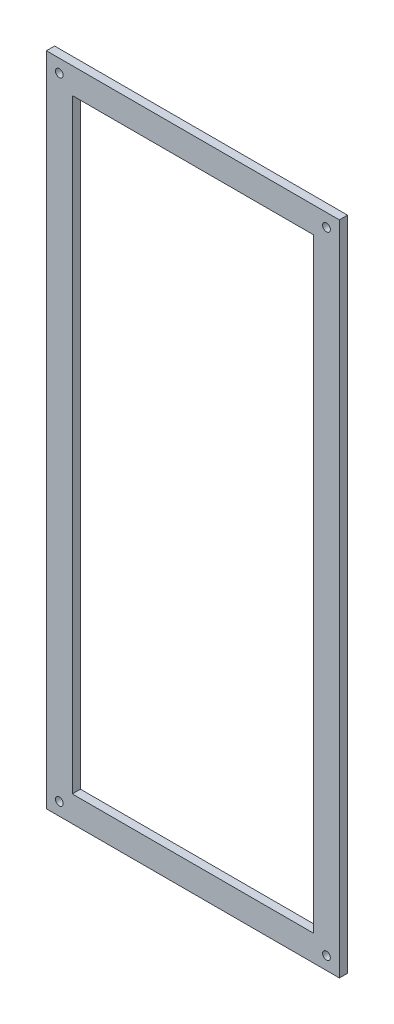
SolidWorks part; units mm, degrees
ref_plane "Front Plane" through (0, 0, 0) normal (0, 0, 1) x (1, 0, 0)
ref_plane "Top Plane" through (0, 0, 0) normal (0, 1, 0) x (1, 0, 0)
ref_plane "Right Plane" through (0, 0, 0) normal (1, 0, 0) x (0, 0, -1)
sketch "Sketch1" plane through (0, 0, 0) normal (0, 0, 1) x (1, 0, 0)
  line L0 (0, 0) -> (0, 254)
  line L1 (0, 254) -> (113.35, 254)
  line L2 (113.35, 254) -> (113.35, 0)
  line L3 (113.35, 0) -> (0, 0)
  line L4 (10, 10) -> (10, 244)
  line L5 (10, 244) -> (103.35, 244)
  line L6 (103.35, 244) -> (103.35, 10)
  line L7 (103.35, 10) -> (10, 10)
  line L8 (56.675, 254) -> (56.675, 0) construction
  line L9 (0, 127) -> (113.35, 127) construction
  circle A0 centre (5, 5) radius 1.5
  circle A1 centre (5, 249) radius 1.5
  circle A2 centre (108.35, 5) radius 1.5
  circle A3 centre (108.35, 249) radius 1.5
  dimension "D7" = 3
  dimension "D1" = 254
  dimension "D2" = 113.35
  dimension "D3" = 10
  dimension "D4" = 10
  dimension "D5" = 10
  dimension "D6" = 10
  dimension "D8" = 5
  dimension "D9" = 5
extrude "Boss-Extrude1" add sketch "Sketch1" along normal blind 3.175
